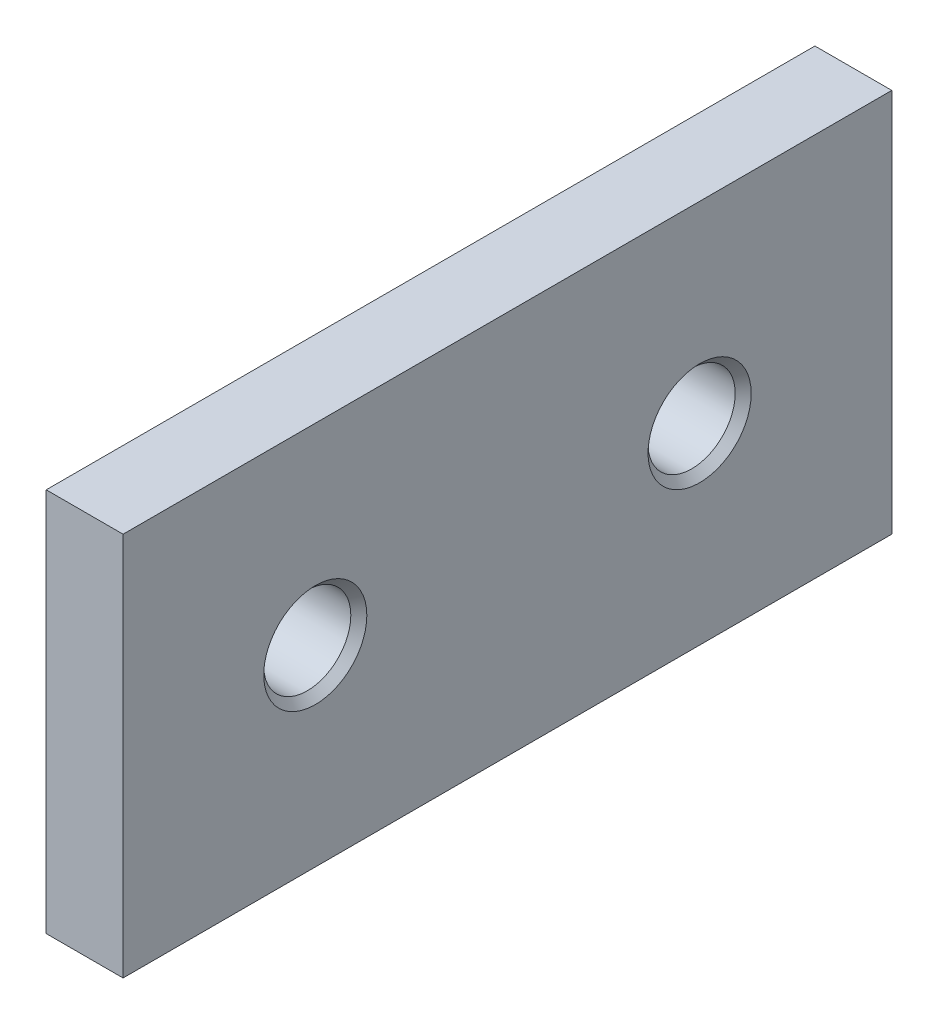
SolidWorks part; units mm, degrees
material "AISI 304"
ref_plane "Спереди" through (0, 0, 0) normal (0, 0, 1) x (1, 0, 0)
ref_plane "Сверху" through (0, 0, 0) normal (0, 1, 0) x (1, 0, 0)
ref_plane "Справа" through (0, 0, 0) normal (1, 0, 0) x (0, 0, -1)
ref_axis "Ось1" through (-62.9241, 0, 0) along (1, 0, 0)
sketch "Эскиз1" plane through (0, 0, 0) normal (0, 0, 1) x (1, 0, 0)
  line L0 (0, 0) -> (53, 0) construction
  line L1 (0, 100) -> (0, 0) construction
  line L2 (0, 102) -> (0.3488, 102)
  line L3 (0, 100) -> (0.3488, 100)
  line L4 (0, 102) -> (0, 100)
  line L5 (51, 0) -> (53, 0)
  line L6 (49.8785, 19.1) -> (51.8921, 19.1)
  arc A0 (0.3488, 102) -> (28.8538, 85.9935) centre (0.3488, 68.6154) cw
  arc A1 (28.8538, 85.9935) -> (53, 0) centre (-112.2, 0) cw
  arc A2 (0.3488, 100) -> (27.1461, 84.9524) centre (0.3488, 68.6154) cw
  arc A3 (27.1461, 84.9524) -> (51, 0) centre (-112.2, 0) cw
  point P0 (0, 101)
  dimension "D3" = 163.2
  dimension "D4" = 31.3846
  dimension "D1" = 204
  dimension "D6" = 38.2
  dimension "D5" = 53
  dimension "D2" = 2
ref_plane "Плоскость1" through (53, 0, 0) normal (1, 0, 0) x (0, 0, -1)
sketch "Эскиз2" plane through (0, 0, 0) normal (0, 0, 1) x (1, 0, 0)
  line L0 (59, 70) -> (53, 70) construction
  line L1 (53, 85) -> (59, 85)
  line L2 (53, 85) -> (53, 55)
  line L3 (53, 55) -> (59, 55)
  line L4 (59, 85) -> (59, 55)
  line L6 (0, 100) -> (0, 0) construction
  line L7 (0, 0) -> (53, 0) construction
  point P13 (56, 70)
  dimension "D1" = 30
  dimension "D2" = 6
  dimension "D3" = 59
  dimension "D4" = 70
ref_plane "Плоскость2" through (56, 0, 0) normal (1, 0, 0) x (0, 0, -1)
sketch "Эскиз3" plane through (56, 0, 0) normal (1, 0, 0) x (0, 0, -1)
  line L0 (0, 0) -> (0, 85) construction
  line L1 (-30, 85) -> (30, 85)
  line L2 (-30, 85) -> (-30, 55)
  line L3 (-30, 55) -> (30, 55)
  line L4 (30, 85) -> (30, 55)
  line L5 (-15, 70) -> (15, 70) construction
  point P7 (-30, 70)
  dimension "D1" = 60
  dimension "D2" = 30
  dimension "D3" = 15
extrude "Бобышка-Вытянуть2" add sketch "Эскиз3" against normal mid plane 6
hole_wizard "Отверстие обработанное метчиком M84" positions "Эскиз13" profile "Эскиз14" tap size "M8" standard "ISO" end condition through all
sketch "Эскиз13" plane through (59, 0, 0) normal (1, 0, 0) x (0, 0, -1)
  point P0 (-15, 70)
  point P2 (15, 70)
sketch "Эскиз14" plane through (59, 70, 15) normal (0, 1, 0) x (0, 0, -1)
  line L0 (0, 0) -> (0, 6)
  line L1 (0, 6) -> (3.4, 6)
  line L2 (3.4, 6) -> (3.4, 0.625)
  line L3 (3.4, 0.625) -> (4.025, 0)
  line L5 (4.025, 0) -> (0, 0)
  line L6 (-3.4, 0.625) -> (-4.025, 0) construction
  line L11 (0, -6.35) -> (0, 107.95) construction
  dimension "Диаметр проходного сверла" = 6.8
  dimension "Глубина проходного сверла" = 6
  dimension "Диаметр передней зенковки" = 8.05
  dimension "Угол передней зенковки" = 90
cosmetic thread "Отверстие резьбы3" parameters "D2"=8
cosmetic thread "Отверстие резьбы4" parameters "D2"=8
equation "\"D\"= 204мм"
equation "\"D1@Эскиз1\"=\"D\""
equation "\"D3@Эскиз1\"=\"D\"*0.8"
equation "\"D4@Эскиз1\"=\"D\"/6.5"
